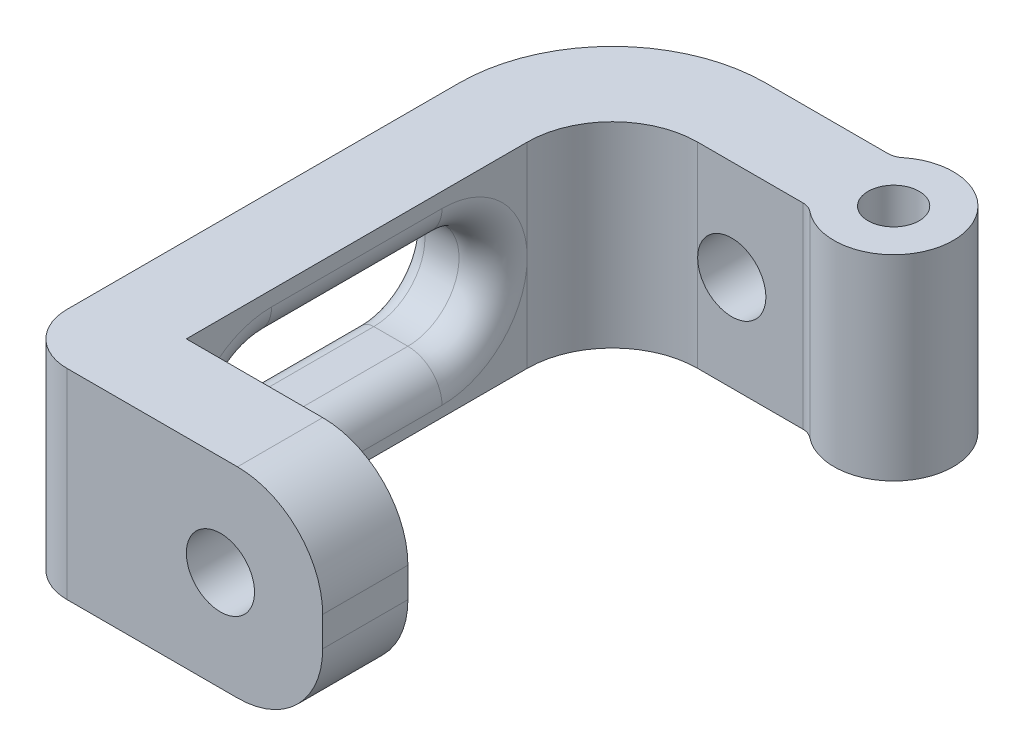
SolidWorks part; units mm, degrees
ref_plane "Front Plane" through (0, 0, 0) normal (0, 0, 1) x (1, 0, 0)
ref_plane "Top Plane" through (0, 0, 0) normal (0, 1, 0) x (1, 0, 0)
ref_plane "Right Plane" through (0, 0, 0) normal (1, 0, 0) x (0, 0, -1)
sketch "Sketch1" plane through (0, 0, 0) normal (0, 0, 1) x (1, 0, 0)
  line L2 (-10, 5.75) -> (10, 5.75)
  line L3 (-10, 5.75) -> (-10, -5.75)
  line L4 (-10, -5.75) -> (10, -5.75)
  line L5 (10, 5.75) -> (10, -5.75)
  line L6 (-10, 5.75) -> (10, -5.75) construction
  line L7 (-10, -5.75) -> (10, 5.75) construction
  point P2 (0, 0)
  dimension "D1" = 20
  dimension "D2" = 11.5
extrude "Boss-Extrude1" add sketch "Sketch1" along normal blind 5
sketch "Sketch2" plane through (0, 0, 5) normal (0, 0, 1) x (1, 0, 0)
  line L0 (-10, -5.75) -> (10, -5.75) construction
  line L1 (-10, 5.75) -> (-5, 5.75)
  line L2 (-10, 5.75) -> (-10, -5.75)
  line L3 (-10, -5.75) -> (-5, -5.75)
  line L4 (-5, 5.75) -> (-5, -5.75)
  dimension "D1" = 5
extrude "Boss-Extrude2" add sketch "Sketch2" along normal blind 25
sketch "Sketch3" plane through (0, 0, 30) normal (0, 0, 1) x (1, 0, 0)
  line L1 (-10, 5.75) -> (8, 5.75)
  line L2 (-10, 5.75) -> (-10, -6)
  line L3 (-10, -6) -> (8, -6)
  line L4 (8, 5.75) -> (8, -6)
  dimension "D1" = 18
  dimension "D2" = 18
extrude "Boss-Extrude3" add sketch "Sketch3" along normal blind 5
sketch "Sketch4" plane through (-10, 0, 0) normal (-1, 0, 0) x (0, 0, 1)
  line L0 (0, -0.125) -> (35, -0.125) construction
  line L1 (35, 5.75) -> (35, -6) construction
  line L2 (15, -0.125) -> (25, -0.125) construction
  line L3 (15, 2.875) -> (25, 2.875)
  line L4 (15, -3.125) -> (25, -3.125)
  arc A0 (15, 2.875) -> (15, -3.125) centre (15, -0.125) ccw
  arc A1 (25, -3.125) -> (25, 2.875) centre (25, -0.125) ccw
  point P7 (20, -0.125)
  dimension "D1" = 15
  dimension "D2" = 10
  dimension "D3" = 3
extrude "Cut-Extrude1" cut sketch "Sketch4" against normal blind 5
sketch "Sketch5" plane through (0, 0, 30) normal (0, 0, -1) x (-1, 0, 0)
  line L0 (-8, -0.125) -> (8.5, -0.125) construction
  line L1 (-8, -6) -> (-8, 5.75) construction
  line L3 (10, 5.75) -> (10, -6) construction
  circle A0 centre (-2, -0.125) radius 2
  dimension "D1" = 4
  dimension "D2" = 12
extrude "Cut-Extrude2" cut sketch "Sketch5" against normal through all both and the other way through all
fillet "Fillet1" radius 9 1 edges at (-10, 0, 0)
fillet "Fillet7" radius 5 2 edges at (8, -6, 32.5) (8, 5.75, 32.5)
fillet "Fillet8" radius 1 4 edges at (-10, -3.125, 20) (-10, -0.125, 12) (-10, 2.875, 20) (-10, -0.125, 28)
fillet "Fillet9" radius 2 4 edges at (-5, -0.125, 12) (-5, 2.875, 20) (-5, -0.125, 28) (-5, -3.125, 20)
sketch "Sketch10" plane through (0, -5.75, 0) normal (0, -1, 0) x (1, 0, 0)
  line L0 (10, 2.5) -> (6, 2.5) construction
  line L1 (10, 5) -> (10, 0) construction
  circle A0 centre (9, 2.5) radius 1.5
  circle A1 centre (9, 2.5) radius 3.5
  dimension "D1" = 3
  dimension "D3" = 7
extrude "Cut-Extrude4" cut sketch "Sketch10" against normal through all both and the other way through all contours A0
extrude "Boss-Extrude7" add sketch "Sketch10<4>" against normal blind 11.5 contours A1 | A0
sketch "Sketch10<4>" plane through (0, -5.75, 0) normal (0, -1, 0) x (1, 0, 0) same geometry as "Sketch10"
fillet "Fillet13" radius 1 2 edges at (6.5505, 0, 0) (6.5505, 0, 5)
fillet "Fillet16" radius 5 1 edges at (-5, 0, 5)
fillet "Fillet17" radius 3 1 edges at (-10, -0.125, 35)
